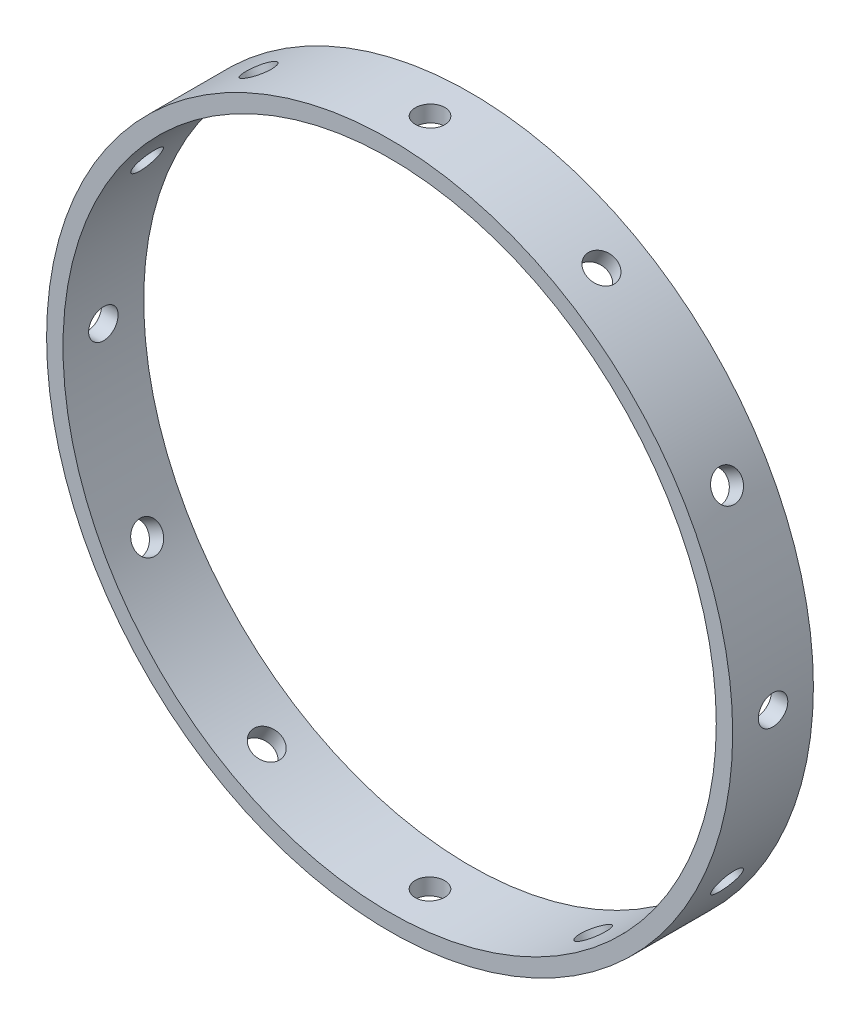
SolidWorks part; units mm, degrees
ref_plane "Front Plane" through (0, 0, 0) normal (0, 0, 1) x (1, 0, 0)
ref_plane "Top Plane" through (0, 0, 0) normal (0, 1, 0) x (1, 0, 0)
ref_plane "Right Plane" through (0, 0, 0) normal (1, 0, 0) x (0, 0, -1)
sketch "Sketch1" plane through (0, 0, 0) normal (0, 0, 1) x (1, 0, 0)
  circle A0 centre (0, 0) radius 77.089
  circle A1 centre (0, 0) radius 80.9625
  dimension "D1" = 154.178
  dimension "D2" = 161.925
extrude "Boss-Extrude1" add sketch "Sketch1" along normal blind 19.05
sketch "Sketch2" plane through (0, 0, 0) normal (0, 1, 0) x (1, 0, 0)
  line L0 (77.089, 0) -> (-77.089, 0) construction
  line L1 (0, -2.0807) -> (0, -15.8358) construction
  circle A0 centre (0, -9.525) radius 3.4782
  dimension "D1" = 9.525
extrude "Cut-Extrude1" cut sketch "Sketch2" against normal through all
ref_axis "Axis1" through (0, 0, 2.0807) along (0, 0, 1)
pattern_circular "CirPattern1" count 12 over 360 about axis through (0, 0, 2.0807) along (0, 0, 1) of "Cut-Extrude1"
